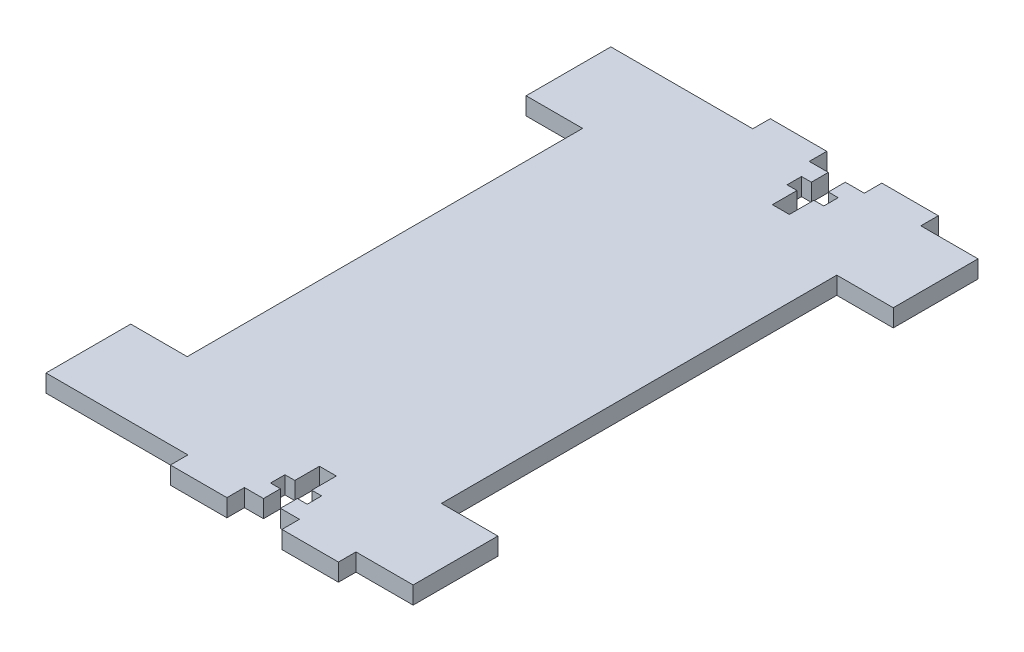
SolidWorks part; units mm, degrees
ref_plane "前视基准面" through (0, 0, 0) normal (0, 0, 1) x (1, 0, 0)
ref_plane "上视基准面" through (0, 0, 0) normal (0, 1, 0) x (1, 0, 0)
ref_plane "右视基准面" through (0, 0, 0) normal (1, 0, 0) x (0, 0, -1)
sketch "草图1" plane through (0, 0, 0) normal (0, 1, 0) x (1, 0, 0)
  line L0 (0, 50) -> (0, -50) construction
  line L1 (-25, -50) -> (25, -50)
  line L2 (-25, -50) -> (-25, 50)
  line L3 (-25, 50) -> (25, 50)
  line L4 (25, -50) -> (25, 50)
  line L5 (-25, -50) -> (25, 50) construction
  line L6 (-25, 50) -> (25, -50) construction
  line L7 (-4.875, -53.1) -> (-14.875, -53.1)
  line L8 (-14.875, -53.1) -> (-14.875, -50)
  line L9 (4.875, -53.1) -> (14.875, -53.1)
  line L10 (14.875, -53.1) -> (14.875, -50)
  line L11 (-25, 0) -> (25, 0) construction
  line L12 (14.875, 53.1) -> (14.875, 50)
  line L13 (4.875, 53.1) -> (14.875, 53.1)
  line L14 (-14.875, 53.1) -> (-14.875, 50)
  line L15 (-4.875, 53.1) -> (-14.875, 53.1)
  line L16 (-25, 35) -> (-15, 35)
  line L17 (-15, 35) -> (-15, -35)
  line L18 (-15, -35) -> (-25, -35)
  line L19 (15, -35) -> (25, -35)
  line L20 (15, 35) -> (15, -35)
  line L21 (25, 35) -> (15, 35)
  line L22 (-25, 50) -> (-40, 50)
  line L23 (-40, 50) -> (-40, -50)
  line L24 (-40, -50) -> (-25, -50)
  line L25 (-40, 35) -> (-30, 35)
  line L26 (-30, 35) -> (-30, -35)
  line L27 (-30, -35) -> (-40, -35)
  point P0 (0, 0)
  line B0 (0, -40.1) -> (0, -51.2019) construction
  line B1 (4.875, -53.1) -> (4.875, -50)
  line B2 (4.875, -50) -> (1.5, -50)
  line B3 (1.5, -50) -> (1.5, -47)
  line B4 (1.5, -47) -> (3.25, -47)
  line B5 (3.25, -47) -> (3.25, -44.45)
  line B6 (3.25, -44.45) -> (1.5, -44.45)
  line B7 (1.5, -44.45) -> (1.5, -40.1)
  line B8 (-1.5, -40.1) -> (1.5, -40.1)
  line B9 (-1.5, -44.45) -> (-1.5, -40.1)
  line B10 (-3.25, -44.45) -> (-1.5, -44.45)
  line B11 (-3.25, -47) -> (-3.25, -44.45)
  line B12 (-1.5, -47) -> (-3.25, -47)
  line B13 (-1.5, -50) -> (-1.5, -47)
  line B14 (-4.875, -50) -> (-1.5, -50)
  line B15 (-4.875, -53.1) -> (-4.875, -50)
  line B16 (0, 40.1) -> (0, 51.2019) construction
  line B17 (4.875, 53.1) -> (4.875, 50)
  line B18 (4.875, 50) -> (1.5, 50)
  line B19 (1.5, 50) -> (1.5, 47)
  line B20 (1.5, 47) -> (3.25, 47)
  line B21 (3.25, 47) -> (3.25, 44.45)
  line B22 (3.25, 44.45) -> (1.5, 44.45)
  line B23 (1.5, 44.45) -> (1.5, 40.1)
  line B24 (-1.5, 40.1) -> (1.5, 40.1)
  line B25 (-1.5, 44.45) -> (-1.5, 40.1)
  line B26 (-3.25, 44.45) -> (-1.5, 44.45)
  line B27 (-3.25, 47) -> (-3.25, 44.45)
  line B28 (-1.5, 47) -> (-3.25, 47)
  line B29 (-1.5, 50) -> (-1.5, 47)
  line B30 (-4.875, 50) -> (-1.5, 50)
  line B31 (-4.875, 53.1) -> (-4.875, 50)
  dimension "D1" = 100
  dimension "D2" = 50
  dimension "D3" = 10
  dimension "D4" = 10
  dimension "D5" = 10
  dimension "D6" = 70
  dimension "D7" = 15
  dimension "D8" = 10
sketch_block_instance "块2-11"
sketch_block "块2"
sketch_block_instance "块2-13"
extrude "凸台-拉伸1" add sketch "草图1" along normal blind 3.1 contours L26 L27 L23 L24 L2 L22 L25 | B29 L3 L2 L16 L17 L18 L1 B13 B12 B11 B10 B9 B8 B7 B6 B5 B4 B3 L4 L19 L20 L21 B19 B20 B21 B22 B23 B24 B25 B26 B27 B28 | L18 L17 L16 L2 | B31 L15 L14 L3 | L13 B17 L3 L12 | L7 B15 L1 L8 | B1 L9 L10 L1 region at (0, 0, 0) region at (-32.5, 0, 48.9888) region at (-9.875, 0, 51.55) region at (-20, 0, 0) region at (-9.875, 0, -51.55) region at (9.875, 0, 51.55) region at (9.875, 0, -51.55)
